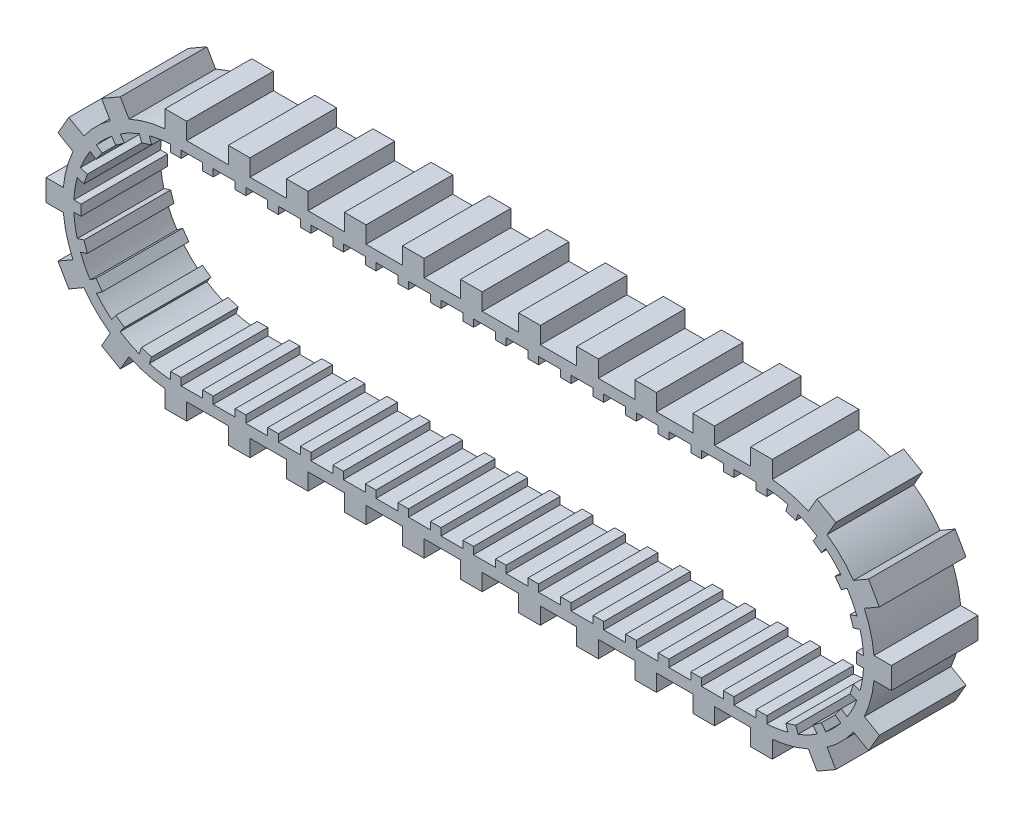
SolidWorks part; units mm, degrees
material "Rubber"
ref_plane "Front Plane" through (0, 0, 0) normal (0, 0, 1) x (1, 0, 0)
ref_plane "Top Plane" through (0, 0, 0) normal (0, 1, 0) x (1, 0, 0)
ref_plane "Right Plane" through (0, 0, 0) normal (1, 0, 0) x (0, 0, -1)
sketch "Sketch1" plane through (0, 0, 0) normal (0, 0, 1) x (1, 0, 0)
  line L0 (0, 29.9339) -> (171.6323, 29.9339)
  line L1 (0, -29.9339) -> (171.6323, -29.9339)
  line L2 (0, 33.1343) -> (171.6323, 33.1343)
  line L3 (0, -33.1343) -> (171.6323, -33.1343)
  arc A0 (0, 29.9339) -> (0, -29.9339) centre (0, 0) ccw
  arc A3 (171.6323, -29.9339) -> (171.6323, 29.9339) centre (171.6323, 0) ccw
  arc A4 (171.6323, -33.1343) -> (171.6323, 33.1343) centre (171.6323, 0) ccw
  arc A5 (0, 33.1343) -> (0, -33.1343) centre (0, 0) ccw
  dimension "D1" = 3.2004
extrude "Boss-Extrude1" add sketch "Sketch1" against normal blind 25.4
sketch "Sketch2" plane through (0, 0, 0) normal (0, 0, 1) x (1, 0, 0)
  line L120 (182.6297, 27.1532) -> (181.6978, 25.9605)
  line L121 (181.6978, 25.9605) -> (178.7483, 26.9188)
  line L122 (178.7483, 26.9188) -> (178.6955, 28.4316)
  line L123 (173.7007, 29.2227) -> (173.183, 27.8003)
  line L124 (173.183, 27.8003) -> (170.0816, 27.8003)
  line L125 (170.0816, 27.8003) -> (169.5639, 29.2227)
  line L126 (164.5691, 28.4316) -> (164.5163, 26.9188)
  line L127 (164.5163, 26.9188) -> (161.5668, 25.9605)
  line L128 (161.5668, 25.9605) -> (160.6349, 27.1532)
  line L129 (156.129, 24.8574) -> (156.5462, 23.4024)
  line L130 (156.5462, 23.4024) -> (154.0372, 21.5795)
  line L131 (154.0372, 21.5795) -> (152.7823, 22.4259)
  line L132 (149.2064, 18.85) -> (150.0528, 17.5951)
  line L133 (150.0528, 17.5951) -> (148.2299, 15.0861)
  line L134 (148.2299, 15.0861) -> (146.7749, 15.5033)
  line L135 (144.479, 10.9974) -> (145.6718, 10.0655)
  line L136 (145.6718, 10.0655) -> (144.7135, 7.116)
  line L137 (144.7135, 7.116) -> (143.2007, 7.0632)
  line L138 (142.4096, 2.0684) -> (143.832, 1.5507)
  line L139 (143.832, 1.5507) -> (143.832, -1.5507)
  line L140 (143.832, -1.5507) -> (142.4096, -2.0684)
  line L141 (143.2007, -7.0632) -> (144.7135, -7.116)
  line L142 (144.7135, -7.116) -> (145.6718, -10.0655)
  line L143 (145.6718, -10.0655) -> (144.479, -10.9974)
  line L144 (146.7749, -15.5033) -> (148.2299, -15.0861)
  line L145 (148.2299, -15.0861) -> (150.0528, -17.5951)
  line L146 (150.0528, -17.5951) -> (149.2064, -18.85)
  line L147 (152.7823, -22.4259) -> (154.0372, -21.5795)
  line L148 (154.0372, -21.5795) -> (156.5462, -23.4024)
  line L149 (156.5462, -23.4024) -> (156.129, -24.8574)
  line L150 (160.6349, -27.1532) -> (161.5668, -25.9605)
  line L151 (161.5668, -25.9605) -> (164.5163, -26.9188)
  line L152 (164.5163, -26.9188) -> (164.5691, -28.4316)
  line L153 (169.5639, -29.2227) -> (170.0816, -27.8003)
  line L154 (170.0816, -27.8003) -> (173.183, -27.8003)
  line L155 (173.183, -27.8003) -> (173.7007, -29.2227)
  line L156 (178.6955, -28.4316) -> (178.7483, -26.9188)
  line L157 (178.7483, -26.9188) -> (181.6978, -25.9605)
  line L158 (181.6978, -25.9605) -> (182.6297, -27.1532)
  line L159 (187.1356, -24.8574) -> (186.7184, -23.4024)
  line L160 (186.7184, -23.4024) -> (189.2274, -21.5795)
  line L161 (189.2274, -21.5795) -> (190.4823, -22.4259)
  line L162 (194.0582, -18.85) -> (193.2117, -17.5951)
  line L163 (193.2117, -17.5951) -> (195.0347, -15.0861)
  line L164 (195.0347, -15.0861) -> (196.4897, -15.5033)
  line L165 (198.7855, -10.9974) -> (197.5928, -10.0655)
  line L166 (197.5928, -10.0655) -> (198.5511, -7.116)
  line L167 (198.5511, -7.116) -> (200.0639, -7.0632)
  line L168 (200.855, -2.0684) -> (199.4326, -1.5507)
  line L169 (199.4326, -1.5507) -> (199.4326, 1.5507)
  line L170 (199.4326, 1.5507) -> (200.855, 2.0684)
  line L171 (200.0639, 7.0632) -> (198.5511, 7.116)
  line L172 (198.5511, 7.116) -> (197.5928, 10.0655)
  line L173 (197.5928, 10.0655) -> (198.7855, 10.9974)
  line L174 (196.4897, 15.5033) -> (195.0347, 15.0861)
  line L175 (195.0347, 15.0861) -> (193.2117, 17.5951)
  line L176 (193.2117, 17.5951) -> (194.0582, 18.85)
  line L177 (190.4823, 22.4259) -> (189.2274, 21.5795)
  line L178 (189.2274, 21.5795) -> (186.7184, 23.4024)
  line L179 (186.7184, 23.4024) -> (187.1356, 24.8574)
  line L240 (-27.1532, 10.9974) -> (-25.9605, 10.0655)
  line L241 (-25.9605, 10.0655) -> (-26.9188, 7.116)
  line L242 (-26.9188, 7.116) -> (-28.4316, 7.0632)
  line L243 (-29.2227, 2.0684) -> (-27.8003, 1.5507)
  line L244 (-27.8003, 1.5507) -> (-27.8003, -1.5507)
  line L245 (-27.8003, -1.5507) -> (-29.2227, -2.0684)
  line L246 (-28.4316, -7.0632) -> (-26.9188, -7.116)
  line L247 (-26.9188, -7.116) -> (-25.9605, -10.0655)
  line L248 (-25.9605, -10.0655) -> (-27.1532, -10.9974)
  line L249 (-24.8574, -15.5033) -> (-23.4024, -15.0861)
  line L250 (-23.4024, -15.0861) -> (-21.5795, -17.5951)
  line L251 (-21.5795, -17.5951) -> (-22.4259, -18.85)
  line L252 (-18.85, -22.4259) -> (-17.5951, -21.5795)
  line L253 (-17.5951, -21.5795) -> (-15.0861, -23.4024)
  line L254 (-15.0861, -23.4024) -> (-15.5033, -24.8574)
  line L255 (-10.9974, -27.1532) -> (-10.0655, -25.9605)
  line L256 (-10.0655, -25.9605) -> (-7.116, -26.9188)
  line L257 (-7.116, -26.9188) -> (-7.0632, -28.4316)
  line L258 (-2.0684, -29.2227) -> (-1.5507, -27.8003)
  line L259 (-1.5507, -27.8003) -> (1.5507, -27.8003)
  line L260 (1.5507, -27.8003) -> (2.0684, -29.2227)
  line L261 (7.0632, -28.4316) -> (7.116, -26.9188)
  line L262 (7.116, -26.9188) -> (10.0655, -25.9605)
  line L263 (10.0655, -25.9605) -> (10.9974, -27.1532)
  line L264 (15.5033, -24.8574) -> (15.0861, -23.4024)
  line L265 (15.0861, -23.4024) -> (17.5951, -21.5795)
  line L266 (17.5951, -21.5795) -> (18.85, -22.4259)
  line L267 (22.4259, -18.85) -> (21.5795, -17.5951)
  line L268 (21.5795, -17.5951) -> (23.4024, -15.0861)
  line L269 (23.4024, -15.0861) -> (24.8574, -15.5033)
  line L270 (27.1532, -10.9974) -> (25.9605, -10.0655)
  line L271 (25.9605, -10.0655) -> (26.9188, -7.116)
  line L272 (26.9188, -7.116) -> (28.4316, -7.0632)
  line L273 (29.2227, -2.0684) -> (27.8003, -1.5507)
  line L274 (27.8003, -1.5507) -> (27.8003, 1.5507)
  line L275 (27.8003, 1.5507) -> (29.2227, 2.0684)
  line L276 (28.4316, 7.0632) -> (26.9188, 7.116)
  line L277 (26.9188, 7.116) -> (25.9605, 10.0655)
  line L278 (25.9605, 10.0655) -> (27.1532, 10.9974)
  line L279 (24.8574, 15.5033) -> (23.4024, 15.0861)
  line L280 (23.4024, 15.0861) -> (21.5795, 17.5951)
  line L281 (21.5795, 17.5951) -> (22.4259, 18.85)
  line L282 (18.85, 22.4259) -> (17.5951, 21.5795)
  line L283 (17.5951, 21.5795) -> (15.0861, 23.4024)
  line L284 (15.0861, 23.4024) -> (15.5033, 24.8574)
  line L285 (10.9974, 27.1532) -> (10.0655, 25.9605)
  line L286 (10.0655, 25.9605) -> (7.116, 26.9188)
  line L287 (7.116, 26.9188) -> (7.0632, 28.4316)
  line L288 (2.0684, 29.2227) -> (1.5507, 27.8003)
  line L289 (1.5507, 27.8003) -> (-1.5507, 27.8003)
  line L290 (-1.5507, 27.8003) -> (-2.0684, 29.2227)
  line L291 (-7.0632, 28.4316) -> (-7.116, 26.9188)
  line L292 (-7.116, 26.9188) -> (-10.0655, 25.9605)
  line L293 (-10.0655, 25.9605) -> (-10.9974, 27.1532)
  line L294 (-15.5033, 24.8574) -> (-15.0861, 23.4024)
  line L295 (-15.0861, 23.4024) -> (-17.5951, 21.5795)
  line L296 (-17.5951, 21.5795) -> (-18.85, 22.4259)
  line L297 (-22.4259, 18.85) -> (-21.5795, 17.5951)
  line L298 (-21.5795, 17.5951) -> (-23.4024, 15.0861)
  line L299 (-23.4024, 15.0861) -> (-24.8574, 15.5033)
  arc A120 (187.1356, 24.8574) -> (186.7414, 25.8409) centre (186.3055, 25.0954) ccw
  arc A121 (186.7414, 25.8409) -> (183.6572, 27.4124) centre (171.6323, 0) ccw
  arc A122 (183.6572, 27.4124) -> (182.6297, 27.1532) centre (183.3103, 26.6216) ccw
  arc A123 (178.6955, 28.4316) -> (178.0166, 29.2452) centre (177.8324, 28.4014) ccw
  arc A124 (178.0166, 29.2452) -> (174.5977, 29.7867) centre (171.6323, 0) ccw
  arc A125 (174.5977, 29.7867) -> (173.7007, 29.2227) centre (174.5122, 28.9273) ccw
  arc A126 (169.5639, 29.2227) -> (168.6668, 29.7867) centre (168.7524, 28.9273) ccw
  arc A127 (168.6668, 29.7867) -> (165.248, 29.2452) centre (171.6323, 0) ccw
  arc A128 (165.248, 29.2452) -> (164.5691, 28.4316) centre (165.4322, 28.4014) ccw
  arc A129 (160.6349, 27.1532) -> (159.6074, 27.4124) centre (159.9543, 26.6216) ccw
  arc A130 (159.6074, 27.4124) -> (156.5232, 25.8409) centre (171.6323, 0) ccw
  arc A131 (156.5232, 25.8409) -> (156.129, 24.8574) centre (156.9591, 25.0954) ccw
  arc A132 (152.7823, 22.4259) -> (151.725, 22.3549) centre (152.2994, 21.7099) ccw
  arc A133 (151.725, 22.3549) -> (149.2774, 19.9072) centre (171.6323, 0) ccw
  arc A134 (149.2774, 19.9072) -> (149.2064, 18.85) centre (149.9224, 19.3329) ccw
  arc A135 (146.7749, 15.5033) -> (145.7913, 15.1091) centre (146.5369, 14.6732) ccw
  arc A136 (145.7913, 15.1091) -> (144.2199, 12.0249) centre (171.6323, 0) ccw
  arc A137 (144.2199, 12.0249) -> (144.479, 10.9974) centre (145.0107, 11.678) ccw
  arc A138 (143.2007, 7.0632) -> (142.3871, 6.3843) centre (143.2309, 6.2001) ccw
  arc A139 (142.3871, 6.3843) -> (141.8456, 2.9654) centre (171.6323, 0) ccw
  arc A140 (141.8456, 2.9654) -> (142.4096, 2.0684) centre (142.705, 2.8799) ccw
  arc A141 (142.4096, -2.0684) -> (141.8456, -2.9654) centre (142.705, -2.8799) ccw
  arc A142 (141.8456, -2.9654) -> (142.3871, -6.3843) centre (171.6323, 0) ccw
  arc A143 (142.3871, -6.3843) -> (143.2007, -7.0632) centre (143.2309, -6.2001) ccw
  arc A144 (144.479, -10.9974) -> (144.2199, -12.0249) centre (145.0107, -11.678) ccw
  arc A145 (144.2199, -12.0249) -> (145.7913, -15.1091) centre (171.6323, 0) ccw
  arc A146 (145.7913, -15.1091) -> (146.7749, -15.5033) centre (146.5369, -14.6732) ccw
  arc A147 (149.2064, -18.85) -> (149.2774, -19.9072) centre (149.9224, -19.3329) ccw
  arc A148 (149.2774, -19.9072) -> (151.725, -22.3549) centre (171.6323, 0) ccw
  arc A149 (151.725, -22.3549) -> (152.7823, -22.4259) centre (152.2994, -21.7099) ccw
  arc A150 (156.129, -24.8574) -> (156.5232, -25.8409) centre (156.9591, -25.0954) ccw
  arc A151 (156.5232, -25.8409) -> (159.6074, -27.4124) centre (171.6323, 0) ccw
  arc A152 (159.6074, -27.4124) -> (160.6349, -27.1532) centre (159.9543, -26.6216) ccw
  arc A153 (164.5691, -28.4316) -> (165.248, -29.2452) centre (165.4322, -28.4014) ccw
  arc A154 (165.248, -29.2452) -> (168.6668, -29.7867) centre (171.6323, 0) ccw
  arc A155 (168.6668, -29.7867) -> (169.5639, -29.2227) centre (168.7524, -28.9273) ccw
  arc A156 (173.7007, -29.2227) -> (174.5977, -29.7867) centre (174.5122, -28.9273) ccw
  arc A157 (174.5977, -29.7867) -> (178.0166, -29.2452) centre (171.6323, 0) ccw
  arc A158 (178.0166, -29.2452) -> (178.6955, -28.4316) centre (177.8324, -28.4014) ccw
  arc A159 (182.6297, -27.1532) -> (183.6572, -27.4124) centre (183.3103, -26.6216) ccw
  arc A160 (183.6572, -27.4124) -> (186.7414, -25.8409) centre (171.6323, 0) ccw
  arc A161 (186.7414, -25.8409) -> (187.1356, -24.8574) centre (186.3055, -25.0954) ccw
  arc A162 (190.4823, -22.4259) -> (191.5395, -22.3549) centre (190.9652, -21.7099) ccw
  arc A163 (191.5395, -22.3549) -> (193.9872, -19.9072) centre (171.6323, 0) ccw
  arc A164 (193.9872, -19.9072) -> (194.0582, -18.85) centre (193.3422, -19.3329) ccw
  arc A165 (196.4897, -15.5033) -> (197.4732, -15.1091) centre (196.7277, -14.6732) ccw
  arc A166 (197.4732, -15.1091) -> (199.0447, -12.0249) centre (171.6323, 0) ccw
  arc A167 (199.0447, -12.0249) -> (198.7855, -10.9974) centre (198.2539, -11.678) ccw
  arc A168 (200.0639, -7.0632) -> (200.8774, -6.3843) centre (200.0337, -6.2001) ccw
  arc A169 (200.8774, -6.3843) -> (201.4189, -2.9654) centre (171.6323, 0) ccw
  arc A170 (201.4189, -2.9654) -> (200.855, -2.0684) centre (200.5596, -2.8799) ccw
  arc A171 (200.855, 2.0684) -> (201.4189, 2.9654) centre (200.5596, 2.8799) ccw
  arc A172 (201.4189, 2.9654) -> (200.8774, 6.3843) centre (171.6323, 0) ccw
  arc A173 (200.8774, 6.3843) -> (200.0639, 7.0632) centre (200.0337, 6.2001) ccw
  arc A174 (198.7855, 10.9974) -> (199.0447, 12.0249) centre (198.2539, 11.678) ccw
  arc A175 (199.0447, 12.0249) -> (197.4732, 15.1091) centre (171.6323, 0) ccw
  arc A176 (197.4732, 15.1091) -> (196.4897, 15.5033) centre (196.7277, 14.6732) ccw
  arc A177 (194.0582, 18.85) -> (193.9872, 19.9072) centre (193.3422, 19.3329) ccw
  arc A178 (193.9872, 19.9072) -> (191.5395, 22.3549) centre (171.6323, 0) ccw
  arc A179 (191.5395, 22.3549) -> (190.4823, 22.4259) centre (190.9652, 21.7099) ccw
  arc A240 (-24.8574, 15.5033) -> (-25.8409, 15.1091) centre (-25.0954, 14.6732) ccw
  arc A241 (-25.8409, 15.1091) -> (-27.4124, 12.0249) centre (0, 0) ccw
  arc A242 (-27.4124, 12.0249) -> (-27.1532, 10.9974) centre (-26.6216, 11.678) ccw
  arc A243 (-28.4316, 7.0632) -> (-29.2452, 6.3843) centre (-28.4014, 6.2001) ccw
  arc A244 (-29.2452, 6.3843) -> (-29.7867, 2.9654) centre (0, 0) ccw
  arc A245 (-29.7867, 2.9654) -> (-29.2227, 2.0684) centre (-28.9273, 2.8799) ccw
  arc A246 (-29.2227, -2.0684) -> (-29.7867, -2.9654) centre (-28.9273, -2.8799) ccw
  arc A247 (-29.7867, -2.9654) -> (-29.2452, -6.3843) centre (0, 0) ccw
  arc A248 (-29.2452, -6.3843) -> (-28.4316, -7.0632) centre (-28.4014, -6.2001) ccw
  arc A249 (-27.1532, -10.9974) -> (-27.4124, -12.0249) centre (-26.6216, -11.678) ccw
  arc A250 (-27.4124, -12.0249) -> (-25.8409, -15.1091) centre (0, 0) ccw
  arc A251 (-25.8409, -15.1091) -> (-24.8574, -15.5033) centre (-25.0954, -14.6732) ccw
  arc A252 (-22.4259, -18.85) -> (-22.3549, -19.9072) centre (-21.7099, -19.3329) ccw
  arc A253 (-22.3549, -19.9072) -> (-19.9072, -22.3549) centre (0, 0) ccw
  arc A254 (-19.9072, -22.3549) -> (-18.85, -22.4259) centre (-19.3329, -21.7099) ccw
  arc A255 (-15.5033, -24.8574) -> (-15.1091, -25.8409) centre (-14.6732, -25.0954) ccw
  arc A256 (-15.1091, -25.8409) -> (-12.0249, -27.4124) centre (0, 0) ccw
  arc A257 (-12.0249, -27.4124) -> (-10.9974, -27.1532) centre (-11.678, -26.6216) ccw
  arc A258 (-7.0632, -28.4316) -> (-6.3843, -29.2452) centre (-6.2001, -28.4014) ccw
  arc A259 (-6.3843, -29.2452) -> (-2.9654, -29.7867) centre (0, 0) ccw
  arc A260 (-2.9654, -29.7867) -> (-2.0684, -29.2227) centre (-2.8799, -28.9273) ccw
  arc A261 (2.0684, -29.2227) -> (2.9654, -29.7867) centre (2.8799, -28.9273) ccw
  arc A262 (2.9654, -29.7867) -> (6.3843, -29.2452) centre (0, 0) ccw
  arc A263 (6.3843, -29.2452) -> (7.0632, -28.4316) centre (6.2001, -28.4014) ccw
  arc A264 (10.9974, -27.1532) -> (12.0249, -27.4124) centre (11.678, -26.6216) ccw
  arc A265 (12.0249, -27.4124) -> (15.1091, -25.8409) centre (0, 0) ccw
  arc A266 (15.1091, -25.8409) -> (15.5033, -24.8574) centre (14.6732, -25.0954) ccw
  arc A267 (18.85, -22.4259) -> (19.9072, -22.3549) centre (19.3329, -21.7099) ccw
  arc A268 (19.9072, -22.3549) -> (22.3549, -19.9072) centre (0, 0) ccw
  arc A269 (22.3549, -19.9072) -> (22.4259, -18.85) centre (21.7099, -19.3329) ccw
  arc A270 (24.8574, -15.5033) -> (25.8409, -15.1091) centre (25.0954, -14.6732) ccw
  arc A271 (25.8409, -15.1091) -> (27.4124, -12.0249) centre (0, 0) ccw
  arc A272 (27.4124, -12.0249) -> (27.1532, -10.9974) centre (26.6216, -11.678) ccw
  arc A273 (28.4316, -7.0632) -> (29.2452, -6.3843) centre (28.4014, -6.2001) ccw
  arc A274 (29.2452, -6.3843) -> (29.7867, -2.9654) centre (0, 0) ccw
  arc A275 (29.7867, -2.9654) -> (29.2227, -2.0684) centre (28.9273, -2.8799) ccw
  arc A276 (29.2227, 2.0684) -> (29.7867, 2.9654) centre (28.9273, 2.8799) ccw
  arc A277 (29.7867, 2.9654) -> (29.2452, 6.3843) centre (0, 0) ccw
  arc A278 (29.2452, 6.3843) -> (28.4316, 7.0632) centre (28.4014, 6.2001) ccw
  arc A279 (27.1532, 10.9974) -> (27.4124, 12.0249) centre (26.6216, 11.678) ccw
  arc A280 (27.4124, 12.0249) -> (25.8409, 15.1091) centre (0, 0) ccw
  arc A281 (25.8409, 15.1091) -> (24.8574, 15.5033) centre (25.0954, 14.6732) ccw
  arc A282 (22.4259, 18.85) -> (22.3549, 19.9072) centre (21.7099, 19.3329) ccw
  arc A283 (22.3549, 19.9072) -> (19.9072, 22.3549) centre (0, 0) ccw
  arc A284 (19.9072, 22.3549) -> (18.85, 22.4259) centre (19.3329, 21.7099) ccw
  arc A285 (15.5033, 24.8574) -> (15.1091, 25.8409) centre (14.6732, 25.0954) ccw
  arc A286 (15.1091, 25.8409) -> (12.0249, 27.4124) centre (0, 0) ccw
  arc A287 (12.0249, 27.4124) -> (10.9974, 27.1532) centre (11.678, 26.6216) ccw
  arc A288 (7.0632, 28.4316) -> (6.3843, 29.2452) centre (6.2001, 28.4014) ccw
  arc A289 (6.3843, 29.2452) -> (2.9654, 29.7867) centre (0, 0) ccw
  arc A290 (2.9654, 29.7867) -> (2.0684, 29.2227) centre (2.8799, 28.9273) ccw
  arc A291 (-2.0684, 29.2227) -> (-2.9654, 29.7867) centre (-2.8799, 28.9273) ccw
  arc A292 (-2.9654, 29.7867) -> (-6.3843, 29.2452) centre (0, 0) ccw
  arc A293 (-6.3843, 29.2452) -> (-7.0632, 28.4316) centre (-6.2001, 28.4014) ccw
  arc A294 (-10.9974, 27.1532) -> (-12.0249, 27.4124) centre (-11.678, 26.6216) ccw
  arc A295 (-12.0249, 27.4124) -> (-15.1091, 25.8409) centre (0, 0) ccw
  arc A296 (-15.1091, 25.8409) -> (-15.5033, 24.8574) centre (-14.6732, 25.0954) ccw
  arc A297 (-18.85, 22.4259) -> (-19.9072, 22.3549) centre (-19.3329, 21.7099) ccw
  arc A298 (-19.9072, 22.3549) -> (-22.3549, 19.9072) centre (0, 0) ccw
  arc A299 (-22.3549, 19.9072) -> (-22.4259, 18.85) centre (-21.7099, 19.3329) ccw
sketch "Sketch3" plane through (0, 0, 0) normal (0, 0, 1) x (1, 0, 0)
  line L0 (-1.5507, 27.8003) -> (1.5507, 27.8003)
  line L1 (1.5507, 27.8003) -> (1.5507, 30.1016)
  line L2 (-1.5507, 27.8003) -> (-1.5507, 30.401)
  line L3 (-1.5507, 30.401) -> (1.5507, 30.1016)
extrude "Boss-Extrude2" add sketch "Sketch3" against normal up to surface (25.4 mm away) up to face at (85.8161, 0, -25.4)
pattern_circular "CirPattern1" count 11 over 180 about axis through (0, 0, -25.4) along (0, 0, 1) of "Boss-Extrude2"
sketch "Sketch4" plane through (0, 0, 0) normal (0, 0, 1) x (1, 0, 0)
  line L0 (85.8161, 29.9339) -> (85.8161, -47.6317) construction
  line L2 (171.6323, 0) -> (0, 0) construction
  point P2 (85.8161, 0)
ref_plane "Plane1" through (85.8161, 0, 0) normal (1, 0, 0) x (0, 0, -1)
mirror "Mirror2" about plane through (85.8161, 0, 0) normal (1, 0, 0) of "CirPattern1"
sketch "Sketch5" plane through (0, 0, 0) normal (0, 0, 1) x (1, 0, 0)
  line L0 (170.0816, 29.9339) -> (1.5507, 29.9339) construction
  line L1 (7.8499, 29.9339) -> (10.9512, 29.9339)
  line L2 (7.8499, 29.9339) -> (7.8499, 27.8003)
  line L3 (7.8499, 27.8003) -> (10.9512, 27.8003)
  line L4 (10.9512, 29.9339) -> (10.9512, 27.8003)
  line L5 (-1.5507, 29.8937) -> (-7.7629, 28.9098) construction
  line L6 (1.5507, 27.8003) -> (-1.5507, 27.8003) construction
  dimension "D1" = 2.1336
  dimension "D2" = 6.2992
extrude "Boss-Extrude3" add sketch "Sketch5" against normal up to surface (25.4 mm away) up to face at (85.8161, 0, -25.4)
pattern_linear "LPattern1" count 17 spacing 9.5377 along (1, 0, 0) of "Boss-Extrude3"
mirror "Mirror3" about plane through (0, 0, 0) normal (0, 1, 0) of "LPattern1"
sketch "Sketch6" plane through (0, 0, 0) normal (0, 0, 1) x (1, 0, 0)
  line L0 (0, 32.9818) -> (0, -6.5119) construction
  line L1 (-3.175, 38.0618) -> (3.175, 38.0618)
  line L2 (-3.175, 38.0618) -> (-3.175, 32.9818)
  line L3 (-3.175, 32.9818) -> (3.175, 32.9818)
  line L4 (3.175, 38.0618) -> (3.175, 32.9818)
  arc A0 (0, 33.1343) -> (0, -33.1343) centre (0, 0) ccw construction
  dimension "D1" = 6.35
  dimension "D2" = 5.08
extrude "Boss-Extrude4" add sketch "Sketch6" against normal up to surface (25.4 mm away) up to face at (85.7469, 0, -25.4)
pattern_circular "CirPattern2" count 7 over 180 about axis through (0, 0, -25.4) along (0, 0, 1) of "Boss-Extrude4"
mirror "Mirror4" about plane through (85.8161, 0, 0) normal (1, 0, 0) of "CirPattern2"
sketch "Sketch10" plane through (0, 0, 0) normal (0, 0, 1) x (1, 0, 0)
  line L0 (168.4573, 33.1343) -> (3.175, 33.1343) construction
  line L1 (15.367, 33.1343) -> (21.717, 33.1343)
  line L2 (15.367, 33.1343) -> (15.367, 38.0618)
  line L3 (15.367, 38.0618) -> (21.717, 38.0618)
  line L4 (21.717, 33.1343) -> (21.717, 38.0618)
  line L5 (3.175, 38.0618) -> (-3.175, 38.0618) construction
  line L6 (3.175, 33.1343) -> (3.175, 38.0618) construction
  dimension "D1" = 12.192
extrude "Boss-Extrude5" add sketch "Sketch10" against normal up to surface (25.4 mm away) up to face at (85.8161, 0, -25.4)
pattern_linear "LPattern2" count 9 spacing 17.018 along (1, 0, 0) of "Boss-Extrude5"
mirror "Mirror5" about plane through (0, 0, 0) normal (0, 1, 0) of "LPattern2"
